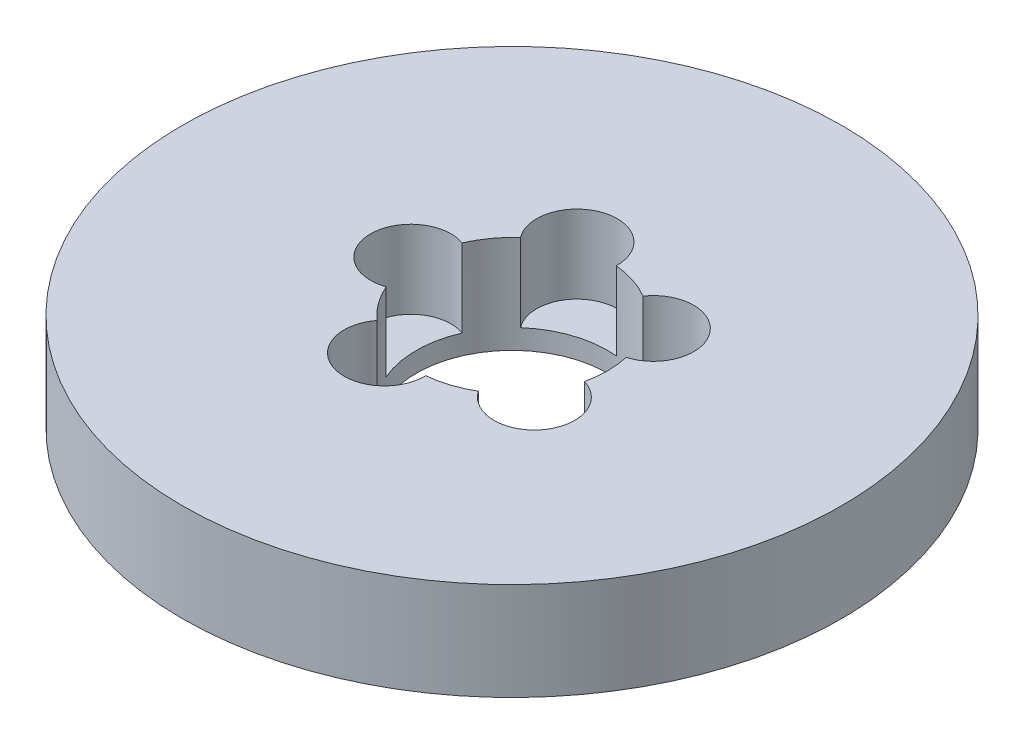
SolidWorks part; units mm, degrees
ref_plane "Front Plane" through (0, 0, 0) normal (0, 0, 1) x (1, 0, 0)
ref_plane "Top Plane" through (0, 0, 0) normal (0, 1, 0) x (1, 0, 0)
ref_plane "Right Plane" through (0, 0, 0) normal (1, 0, 0) x (0, 0, -1)
sketch "Sketch1" plane through (0, 0, 0) normal (0, 1, 0) x (1, 0, 0)
  circle A0 centre (0, 0) radius 77.5
  dimension "FLANGE_OD" = 155
extrude "Boss-Extrude1" add sketch "Sketch1" along normal blind 23
sketch "Sketch2" plane through (0, 0, 0) normal (0, 1, 0) x (1, 0, 0)
  circle A0 centre (0, 0) radius 22.5
  dimension "BORE_D" = 45
extrude "Cut-Extrude1" cut sketch "Sketch2" along normal through all
sketch "Sketch3" plane through (0, 23, 0) normal (0, 1, 0) x (1, 0, 0)
  circle A0 centre (0, 0) radius 23.7987 construction
  circle A1 centre (-23.7987, 0) radius 9.4785
  dimension "BOLT_D" = 18.957
  dimension "BOLT_PCD" = 47.5974
extrude "Cut-Extrude2" cut sketch "Sketch3" against normal blind 18.3455
pattern_circular "CirPattern1" count 5 over 360 about axis through (0, 0, 0) along (0, 1, 0) of "Cut-Extrude2"
